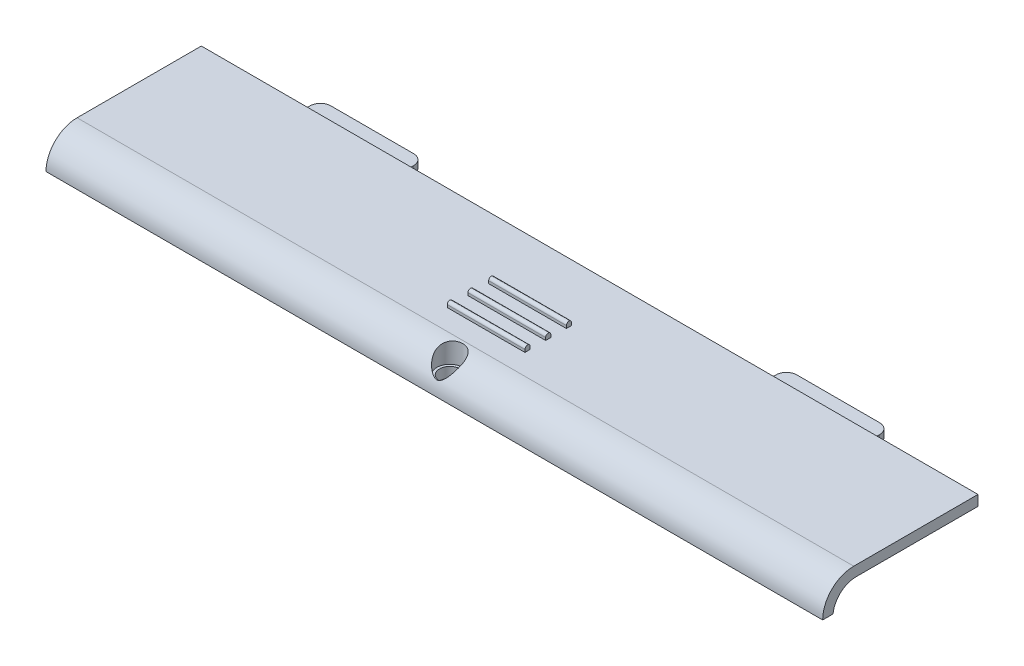
SolidWorks part; units mm, degrees
ref_plane "Front Plane" through (0, 0, 0) normal (0, 0, 1) x (1, 0, 0)
ref_plane "Top Plane" through (0, 0, 0) normal (0, 1, 0) x (1, 0, 0)
ref_plane "Right Plane" through (0, 0, 0) normal (1, 0, 0) x (0, 0, -1)
sketch "Sketch1" plane through (0, 0, 0) normal (0, 1, 0) x (1, 0, 0)
  line L1 (0, 0) -> (150, 0)
  line L2 (0, 0) -> (0, 30)
  line L3 (0, 30) -> (150, 30)
  line L4 (150, 0) -> (150, 30)
  dimension "D1" = 30
  dimension "D2" = 150
extrude "Boss-Extrude1" add sketch "Sketch1" against normal blind 6
sketch "Sketch2" plane through (150, 0, 0) normal (1, 0, 0) x (0, 0, -1)
  line L1 (30, -6) -> (2, -6)
  line L2 (30, -6) -> (30, -2)
  line L3 (30, -2) -> (2, -2)
  line L4 (2, -6) -> (2, -2)
  dimension "D1" = 28
  dimension "D2" = 4
extrude "Cut-Extrude1" cut sketch "Sketch2" against normal blind 150
fillet "Fillet1" radius 4.5 1 edges at (75, -2, -2)
sketch "Sketch3" plane through (0, -6, 0) normal (0, -1, 0) x (1, 0, 0)
  line L0 (0, 0) -> (150, 0) construction
  line L1 (72, 0) -> (78, 0)
  line L2 (72, 0) -> (72, -3)
  line L3 (72, -3) -> (78, -3)
  line L4 (78, 0) -> (78, -3)
  line L5 (150, -30) -> (150, -6.4721) construction
  circle A0 centre (75, -3) radius 3
  line M5 (0, -2) -> (150, -2)
  line M7 (150, 0) -> (0, 0)
  dimension "D3" = 75
  dimension "D1" = 6
  dimension "D2" = 3
extrude "Boss-Extrude3" add sketch "Sketch3" against normal blind 6 contours L3 A0 | A0 M5 | L3 A0 M5 | A0 L4 M5 M7 region at (77.3112, -6, -0.6225) region at (75, -6, -1.1716) region at (75, -6, -2.5048) region at (75, -6, -4.2732)
sketch "Sketch6" plane through (0, -6, 0) normal (0, -1, 0) x (-1, 0, 0)
  circle A0 centre (-75, 3) radius 2
extrude "Cut-Extrude4" cut sketch "Sketch6" against normal blind 6
sketch "Sketch7" plane through (0, 0, 0) normal (0, 1, 0) x (1, 0, 0)
  circle A0 centre (75, 3) radius 2.5
extrude "Cut-Extrude5" cut sketch "Sketch7" against normal blind 4
fillet "Fillet4" radius 6 1 edges at (75, 0, 0)
sketch "Sketch8" plane through (0, 0, -30) normal (0, 0, -1) x (-1, 0, 0)
  line L0 (0, -2) -> (-150, -2) construction
  line L1 (-40, -0.5) -> (-20, -0.5)
  line L2 (-40, -0.5) -> (-40, -2)
  line L3 (-40, -2) -> (-20, -2)
  line L4 (-20, -0.5) -> (-20, -2)
  line L5 (0, -2) -> (0, 0) construction
  line L6 (-150, -2) -> (-150, 0) construction
  line L7 (-130, -0.5) -> (-110, -0.5)
  line L8 (-130, -0.5) -> (-130, -2)
  line L9 (-130, -2) -> (-110, -2)
  line L10 (-110, -0.5) -> (-110, -2)
  dimension "D1" = 1.5
  dimension "D2" = 20
  dimension "D3" = 20
  dimension "D4" = 1.5
  dimension "D5" = 20
  dimension "D6" = 20
extrude "Boss-Extrude4" add sketch "Sketch8" along normal blind 3
fillet "Fillet5" radius 2 4 edges at (20, -1.25, -33) (40, -1.25, -33) (130, -1.25, -33) (110, -1.25, -33)
sketch "Sketch9" plane through (0, 0, 0) normal (0, 1, 0) x (1, 0, 0)
  line L0 (67.5, 15) -> (82.5, 15)
  line L1 (67.5, 11) -> (82.5, 11)
  line L2 (67.5, 11) -> (67.5, 10)
  line L3 (67.5, 10) -> (82.5, 10)
  line L4 (82.5, 11) -> (82.5, 10)
  line L5 (67.5, 15) -> (67.5, 14)
  line L6 (67.5, 14) -> (82.5, 14)
  line L7 (82.5, 15) -> (82.5, 14)
  line L8 (67.5, 19) -> (82.5, 19)
  line L9 (67.5, 19) -> (67.5, 18)
  line L10 (67.5, 18) -> (82.5, 18)
  line L11 (82.5, 19) -> (82.5, 18)
  line L12 (0, 6) -> (150, 6) construction
  line L13 (150, 6) -> (150, 30) construction
  point P12 (82.5, 10.5)
  dimension "D1" = 15
  dimension "D2" = 1
  dimension "D3" = 15
  dimension "D4" = 15
  dimension "D5" = 0
  dimension "D6" = 0
  dimension "D7" = 3
  dimension "D8" = 1
  dimension "D9" = 1
  dimension "D10" = 3
  dimension "D11" = 4
  dimension "D12" = 67.5
extrude "Boss-Extrude5" add sketch "Sketch9" along normal blind 1
sketch "Sketch11" plane through (82.5, 0, 0) normal (1, 0, 0) x (0, 0, -1)
  line L0 (18, 1) -> (18, 0) construction
  line L1 (19, 1) -> (19, 0) construction
  arc A0 (18, 0.5) -> (19, 0.5) centre (18.5, 0.5) cw
extrude "Cut-Extrude6" cut sketch "Sketch11" against normal blind 15 and the other way through all
sketch "Sketch12" plane through (82.5, 0, 0) normal (1, 0, 0) x (0, 0, -1)
  line L0 (14, 1) -> (14, 0) construction
  line L1 (15, 1) -> (15, 0) construction
  arc A0 (14, 0.5) -> (15, 0.5) centre (14.5, 0.5) cw
extrude "Cut-Extrude7" cut sketch "Sketch12" against normal blind 15 and the other way through all
sketch "Sketch13" plane through (82.5, 0, 0) normal (1, 0, 0) x (0, 0, -1)
  line L0 (10, 1) -> (10, 0) construction
  line L1 (11, 1) -> (11, 0) construction
  arc A0 (10, 0.5) -> (11, 0.5) centre (10.5, 0.5) cw
extrude "Cut-Extrude8" cut sketch "Sketch13" against normal blind 15 and the other way through all
